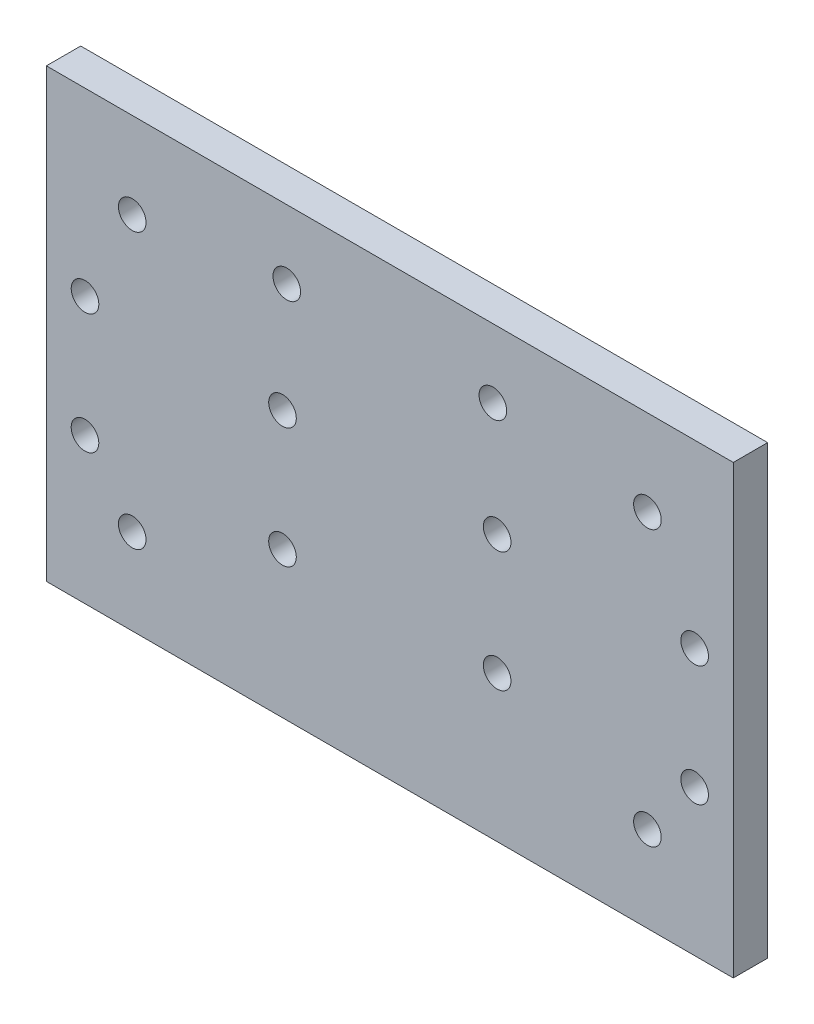
SolidWorks part; units mm, degrees
material "6061 Alloy"
ref_plane "Front Plane" through (0, 0, 0) normal (0, 0, 1) x (1, 0, 0)
ref_plane "Top Plane" through (0, 0, 0) normal (0, 1, 0) x (1, 0, 0)
ref_plane "Right Plane" through (0, 0, 0) normal (1, 0, 0) x (0, 0, -1)
sketch "Sketch1" plane through (0, 0, 0) normal (0, 0, 1) x (1, 0, 0)
  line L1 (-63.5, 41.275) -> (63.5, 41.275)
  line L2 (-63.5, 41.275) -> (-63.5, -41.275)
  line L3 (-63.5, -41.275) -> (63.5, -41.275)
  line L4 (63.5, 41.275) -> (63.5, -41.275)
  line L5 (-63.5, 41.275) -> (63.5, -41.275) construction
  line L6 (-63.5, -41.275) -> (63.5, 41.275) construction
  point P0 (0, 0)
  dimension "D1" = 127
  dimension "D2" = 82.55
extrude "Boss-Extrude1" add sketch "Sketch1" along normal blind 6.35
hole_wizard "Tapped Hole for #10-32 Helicoil1" positions "Sketch3" profile "Sketch4" tap size "#10-32" standard "Helicoil® Inch" end condition up to next
sketch "Sketch3" plane through (0, 0, 0) normal (0, 0, -1) x (-1, 0, 0)
  line L1 (-56.3565, 7.9375) -> (-19.844, 7.9375) construction
  line L2 (-56.3565, 7.9375) -> (-56.3565, -14.2875) construction
  line L3 (-56.3565, -14.2875) -> (-19.844, -14.2875) construction
  line L4 (-19.844, 7.9375) -> (-19.844, -14.2875) construction
  line L6 (19.844, 7.9375) -> (56.3565, 7.9375) construction
  line L7 (19.844, 7.9375) -> (19.844, -14.2875) construction
  line L8 (19.844, -14.2875) -> (56.3565, -14.2875) construction
  line L9 (56.3565, 7.9375) -> (56.3565, -14.2875) construction
  line L10 (0, 0) -> (0, -3.175) construction
  line L12 (-19.844, -3.175) -> (19.844, -3.175) construction
  line L13 (0, 0) -> (0, 28.575) construction
  line L15 (-19.05, 28.575) -> (19.05, 28.575) construction
  line L16 (63.5, -41.275) -> (-63.5, -41.275) construction
  point P0 (-56.3565, 7.9375)
  point P1 (-19.844, -14.2875)
  point P138 (-56.3565, -14.2875)
  point P139 (-19.844, 7.9375)
  point P140 (19.844, 7.9375)
  point P141 (56.3565, -14.2875)
  point P310 (19.844, -14.2875)
  point P311 (56.3565, 7.9375)
  point P347 (-19.05, 28.575)
  point P348 (19.05, 28.575)
  dimension "D1" = 22.225
  dimension "D2" = 36.5125
  dimension "D3" = 39.688
  dimension "D4" = 38.1
  dimension "D5" = 31.75
  dimension "D6" = 26.9875
sketch "Sketch4" plane through (56.3565, 7.9375, 0) normal (1, 0, 0) x (0, 1, 0)
  line L0 (0, 0) -> (0, 6.35)
  line L1 (0, 6.35) -> (2.5527, 6.35)
  line L2 (2.5527, 6.35) -> (2.5527, 0)
  line L5 (2.5527, 0) -> (0, 0)
  line L11 (0, -6.35) -> (0, 107.95) construction
  dimension "Thru Tap Drill Dia." = 5.1054
  dimension "Thru Tap Drill Depth" = 6.35
cosmetic thread "Hole Thread1" parameters "D1"=5.588, "D2"=5.936
cosmetic thread "Hole Thread2" parameters "D1"=5.588, "D2"=5.936
cosmetic thread "Hole Thread3" parameters "D1"=5.588, "D2"=5.936
cosmetic thread "Hole Thread4" parameters "D1"=5.588, "D2"=5.936
cosmetic thread "Hole Thread5" parameters "D1"=5.588, "D2"=5.936
cosmetic thread "Hole Thread6" parameters "D1"=5.588, "D2"=5.936
cosmetic thread "Hole Thread7" parameters "D1"=5.588, "D2"=5.936
cosmetic thread "Hole Thread8" parameters "D1"=5.588, "D2"=5.936
cosmetic thread "Hole Thread9" parameters "D1"=5.588, "D2"=5.936
cosmetic thread "Hole Thread10" parameters "D1"=5.588, "D2"=5.936
hole_wizard "Tapped Hole for #10-32 Helicoil2" positions "Sketch6" profile "Sketch5" tap size "#10-32" standard "Helicoil® Inch" end condition up to next
sketch "Sketch6" plane through (0, 0, 0) normal (0, 0, -1) x (-1, 0, 0)
  line L1 (-47.625, 25.4) -> (47.625, 25.4) construction
  line L2 (-47.625, 25.4) -> (-47.625, -25.4) construction
  line L3 (-47.625, -25.4) -> (47.625, -25.4) construction
  line L4 (47.625, 25.4) -> (47.625, -25.4) construction
  line L5 (-47.625, -25.4) -> (47.625, 25.4) construction
  point P0 (-47.625, 25.4)
  point P1 (47.625, -25.4)
  point P190 (-47.625, -25.4)
  point P191 (47.625, 25.4)
  dimension "D1" = 50.8
  dimension "D2" = 95.25
cosmetic thread "Hole Thread13" parameters "D1"=5.588, "D2"=5.936
cosmetic thread "Hole Thread14" parameters "D1"=5.588, "D2"=5.936
cosmetic thread "Hole Thread15" parameters "D1"=5.588, "D2"=5.936
cosmetic thread "Hole Thread16" parameters "D1"=5.588, "D2"=5.936
sketch "Sketch5" plane through (47.625, 25.4, 0) normal (1, 0, 0) x (0, 1, 0)
  line L0 (0, 0) -> (0, 6.35)
  line L1 (0, 6.35) -> (2.5527, 6.35)
  line L2 (2.5527, 6.35) -> (2.5527, 0)
  line L5 (2.5527, 0) -> (0, 0)
  line L11 (0, -6.35) -> (0, 107.95) construction
  dimension "Thru Tap Drill Dia." = 5.1054
  dimension "Thru Tap Drill Depth" = 6.35
ref_plane "Plane1" through (0, -25.4, 0) normal (0, -1, 0) x (-1, 0, 0)
ref_plane "Plane2" through (0, 25.4, 0) normal (0, -1, 0) x (-1, 0, 0)
